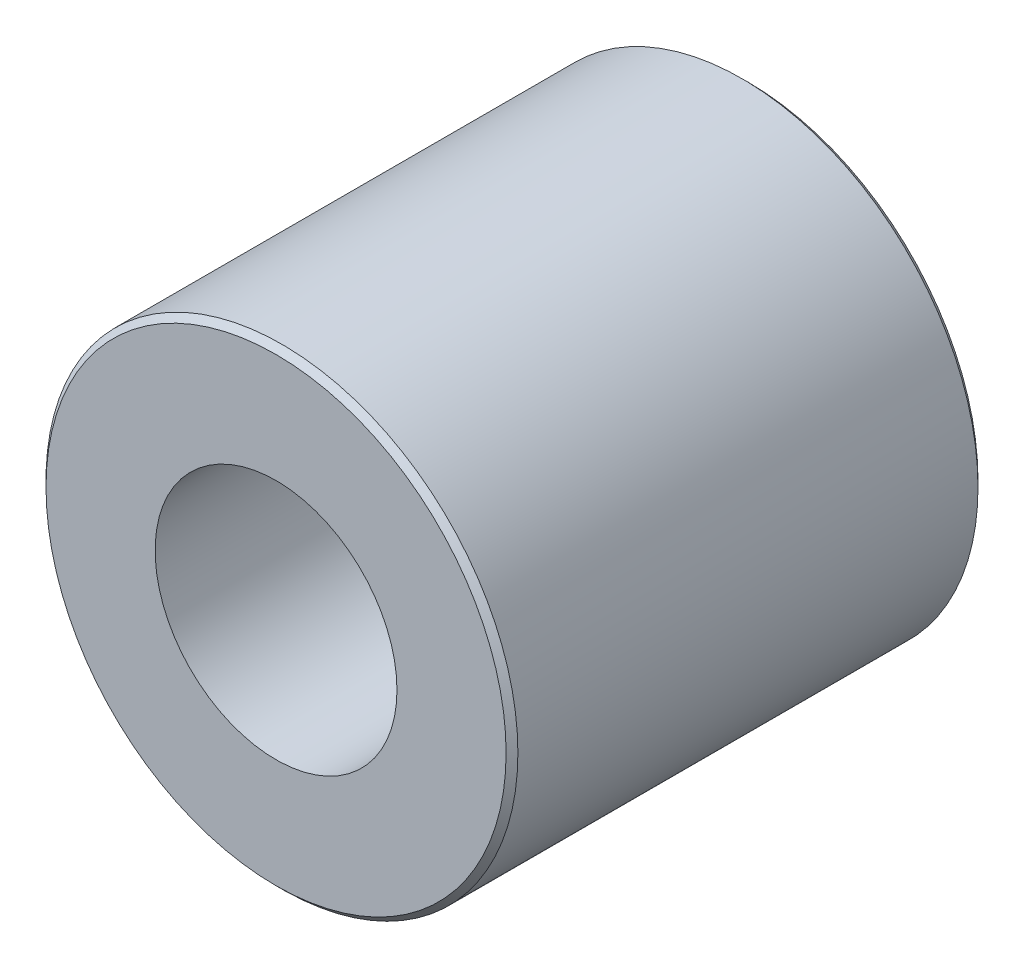
SolidWorks part; units mm, degrees
material "Laiton"
ref_plane "Plan de face" through (0, 0, 0) normal (0, 0, 1) x (1, 0, 0)
ref_plane "Plan de dessus" through (0, 0, 0) normal (0, 1, 0) x (1, 0, 0)
ref_plane "Plan de droite" through (0, 0, 0) normal (1, 0, 0) x (0, 0, -1)
sketch "Esquisse1" plane through (0, 0, 0) normal (0, 0, 1) x (1, 0, 0)
  circle A0 centre (0, 0) radius 2
  circle A1 centre (0, 0) radius 1.06
  dimension "D1" = 4
  dimension "D2" = 2.12
extrude "Extrusion1" add sketch "Esquisse1" along normal blind 4
ref_axis "Taraudage1-Axe" through (0, 0, 4) along (0, 0, -1)
ref_plane "Taraudage1-PlanEnBout" through (0, 0, 4) normal (0, 0, 1) x (1, 0, 0)
sketch "Esquisse2" plane through (0, 0, 4) normal (0, 0, 1) x (1, 0, 0)
  circle A0 centre (0, 0) radius 1.06
  dimension "D1" = 2.12
curve "Hélice/Spirale1" pitch 0.35 height 5 turns 14.2857
ref_plane "Taraudage1-PlanTransversal" through (0.918, 0.53, 4) normal (-0.5, 0.866, 0) x (-0.866, -0.5, 0)
sketch "Esquisse3" plane through (0.918, 0.53, 4) normal (-0.5, 0.866, 0) x (-0.866, -0.5, 0)
  line L0 (0, 0) -> (0.021, 0) construction
  line L1 (0.021, 0.1434) -> (0.021, -0.1434)
  line L2 (0.021, -0.1434) -> (-0.2019, -0.0147)
  line L3 (-0.2019, -0.0147) -> (-0.2019, 0.0147)
  line L4 (0.021, 0.1434) -> (-0.2019, 0.0147)
  line L6 (1.06, 0) -> (1.06, -4) construction
  point P6 (-0.2019, 0)
  dimension "D1" = 0.021
  dimension "D2" = 0.1434
  dimension "D3" = 120
  dimension "D4" = 0.2229
  dimension "D5" = 90
sweep "Enlèvement de matière-Balayage1" [suppressed] cut profiles "Esquisse3" path "Hélice/Spirale1"
sketch "Esquisse4" plane through (0, 0, 4) normal (0, 0, 1) x (1, 0, 0)
  circle A1 centre (0, 0) radius 1.06
  circle A2 centre (0, 0) radius 1.06
  dimension "D1" = 0
curve "Hélice/Spirale2" pitch 0.35 height 0.175 turns 0.5
sketch "Esquisse5" plane through (0.918, 0.53, 4) normal (-0.5, 0.866, 0) x (-0.866, -0.5, 0)
  line L4 (0.021, -0.1434) -> (0.021, 0.1434)
  line L5 (-0.2019, -0.0147) -> (0.021, -0.1434)
  line L6 (-0.2019, 0.0147) -> (-0.2019, -0.0147)
  line L7 (0.021, 0.1434) -> (-0.2019, 0.0147)
  line L8 (0.021, -0.1434) -> (0.021, 0.1434)
  line L9 (-0.2019, -0.0147) -> (0.021, -0.1434)
  line L10 (-0.2019, 0.0147) -> (-0.2019, -0.0147)
  line L11 (0.021, 0.1434) -> (-0.2019, 0.0147)
  dimension "D1" = 0
sweep "Enlèvement de matière-Balayage2" [suppressed] cut profiles "Esquisse5" path "Hélice/Spirale2"
chamfer "Chanfrein1" distance 0.05 angle 45 2 edges at (2, 0, 0) (2, 0, 4)
other "SupprimerFace1" face at (1.06, 0, 4) and patch yes
hole_wizard "Trou taraudé M2.51" positions "Esquisse7" profile "Esquisse6" tap size "M2.5" standard "Iso" end condition through all
sketch "Esquisse7" plane through (0, 0, 4) normal (0, 0, 1) x (1, 0, 0)
  point P0 (0, 0)
sketch "Esquisse6" plane through (0, 0, 4) normal (1, 0, 0) x (0, -1, 0)
  line L0 (0, 0) -> (0, 4)
  line L1 (0, 4) -> (1.025, 4)
  line L2 (1.025, 4) -> (1.025, 0)
  line L5 (1.025, 0) -> (0, 0)
  line L11 (0, -6.35) -> (0, 107.95) construction
  dimension "Diamètre du trou pour taraudage jusqu'au prochain" = 2.05
  dimension "Profondeur du trou pour taraudage jusqu'au prochain" = 4
cosmetic thread "Filetage de perçage1" parameters "D2"=2.5
